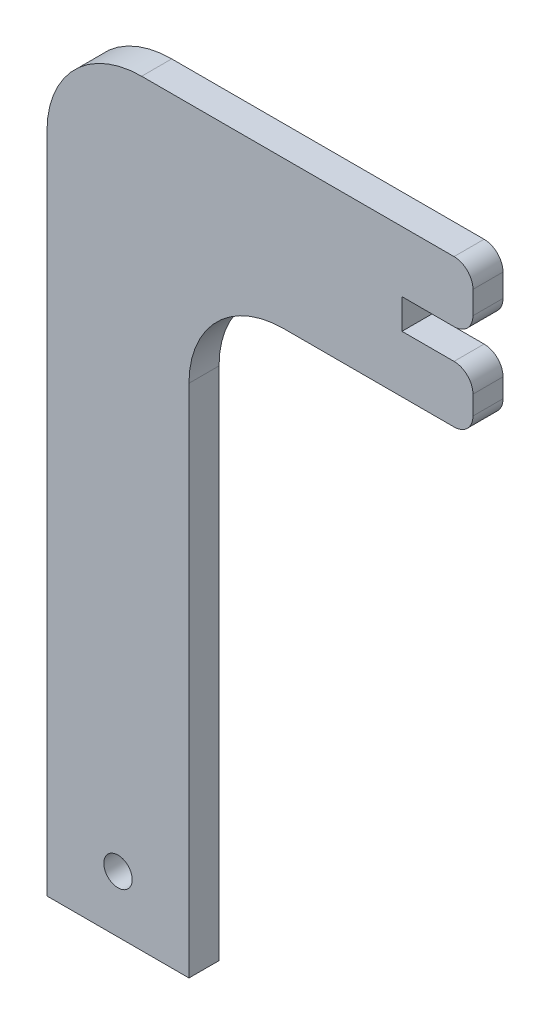
SolidWorks part; units mm, degrees
ref_plane "Front Plane" through (0, 0, 0) normal (0, 0, 1) x (1, 0, 0)
ref_plane "Top Plane" through (0, 0, 0) normal (0, 1, 0) x (1, 0, 0)
ref_plane "Right Plane" through (0, 0, 0) normal (1, 0, 0) x (0, 0, -1)
sketch "Sketch1" plane through (0, 0, 0) normal (0, 0, 1) x (1, 0, 0)
  line L1 (0, 0) -> (-45, 0)
  line L2 (0, 0) -> (0, -80)
  line L3 (0, -80) -> (-45, -80)
  line L4 (-45, 0) -> (-45, -80)
  dimension "D1" = 45
  dimension "D2" = 80
extrude "Boss-Extrude1" add sketch "Sketch1" along normal blind 3.175
sketch "Sketch2" plane through (0, 0, 3.175) normal (0, 0, 1) x (1, 0, 0)
  line L0 (0, -80) -> (0, 0) construction
  line L1 (-7.5, -6.4125) -> (7.5, -6.4125)
  line L2 (-7.5, -6.4125) -> (-7.5, -9.5875)
  line L3 (-7.5, -9.5875) -> (7.5, -9.5875)
  line L4 (7.5, -6.4125) -> (7.5, -9.5875)
  line L5 (-7.5, -6.4125) -> (7.5, -9.5875) construction
  line L6 (-7.5, -9.5875) -> (7.5, -6.4125) construction
  line L7 (0, 0) -> (-45, 0) construction
  point P0 (0, -8)
  dimension "D1" = 15
  dimension "D2" = 3.175
  dimension "D3" = 8
extrude "Cut-Extrude1" cut sketch "Sketch2" against normal through all
sketch "Sketch3" plane through (0, 0, 3.175) normal (0, 0, 1) x (1, 0, 0)
  line L0 (-7.5, -9.5875) -> (0, -9.5875) construction
  line L1 (0, -80) -> (-30, -80)
  line L2 (0, -80) -> (0, -15.5875)
  line L3 (0, -15.5875) -> (-30, -15.5875)
  line L4 (-30, -80) -> (-30, -15.5875)
  line L5 (-45, 0) -> (-45, -80) construction
  line L6 (-45, -80) -> (0, -80) construction
  circle A0 centre (-37.5, -74) radius 1.5
  dimension "D3" = 3
  dimension "D1" = 6
  dimension "D2" = 15
  dimension "D4" = 6
  dimension "D5" = 7.5
extrude "Cut-Extrude2" cut sketch "Sketch3" against normal through all
fillet "Fillet1" radius 10 2 edges at (-45, 0, 1.5875) (-30, -15.5875, 1.5875)
fillet "Fillet2" radius 2 4 edges at (0, -15.5875, 1.5875) (0, 0, 1.5875) (0, -9.5875, 1.5875) (0, -6.4125, 1.5875)
